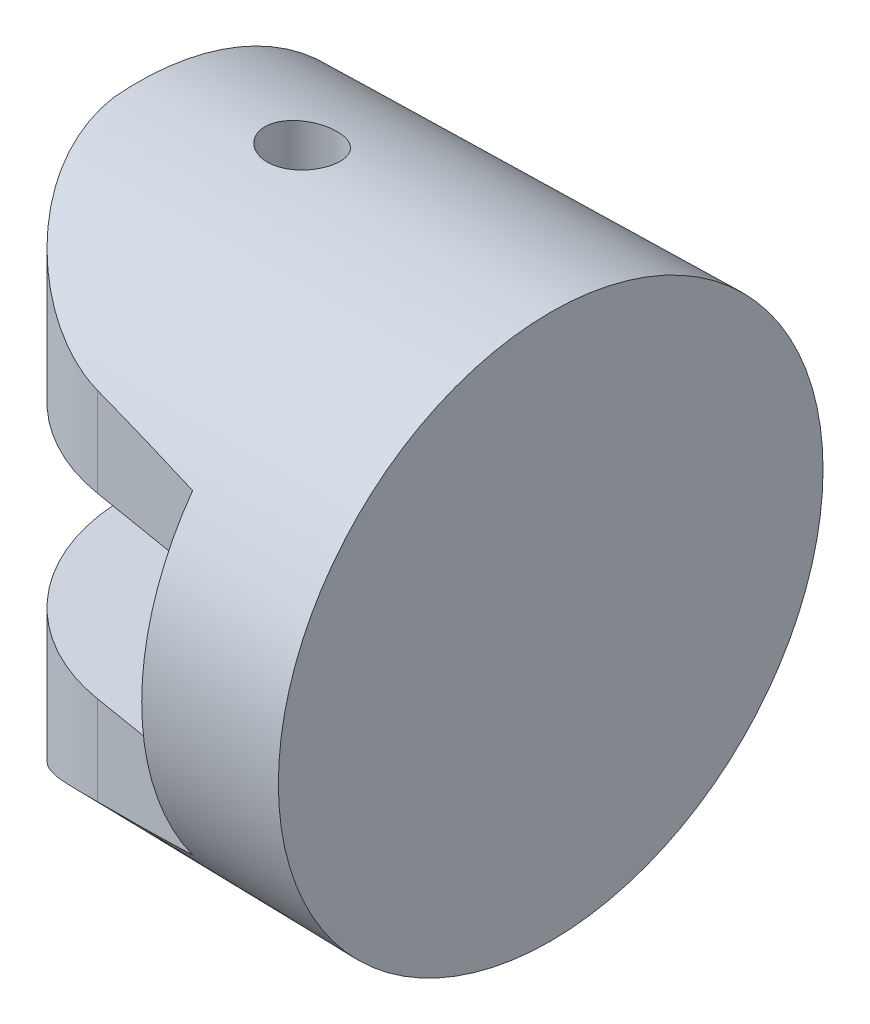
SolidWorks part; units mm, degrees
ref_plane "Ön Düzlem" through (0, 0, 0) normal (0, 0, 1) x (1, 0, 0)
ref_plane "Üst Düzlem" through (0, 0, 0) normal (0, 1, 0) x (1, 0, 0)
ref_plane "Sağ Düzlem" through (0, 0, 0) normal (1, 0, 0) x (0, 0, -1)
sketch "Sketch1" plane through (0, 0, 0) normal (1, 0, 0) x (0, 0, -1)
  circle A0 centre (0, 0) radius 10
  dimension "D1" = 20
extrude "Boss-Extrude1" add sketch "Sketch1" along normal blind 18
sketch "Sketch2" plane through (0, 0, 0) normal (0, 1, 0) x (1, 0, 0)
  line L0 (10, 9.0632) -> (0, 9.0632)
  line L1 (18, -10) -> (18, 10) construction
  line L2 (10, -8) -> (5.8413, -7.3121)
  line L3 (0, 9.0632) -> (0, -0.8843)
  line L5 (0, 10) -> (0, -10) construction
  line L6 (10, -8) -> (10, -11.2528)
  line L9 (10, -11.2528) -> (-2.5986, -11.2528)
  line L10 (-2.5986, -11.2528) -> (-2.5986, 12.4635)
  line L11 (-2.5986, 12.4635) -> (10, 12.4635)
  line L12 (10, 12.4635) -> (10, 9.0632)
  arc A0 (0, -0.8843) -> (5.8413, -7.3121) centre (6.9836, -0.4059) ccw
  dimension "D2" = 7
  dimension "D1" = 8
  dimension "D4" = 8
  dimension "D5" = 2
extrude "Cut-Extrude1" cut sketch "Sketch2" against normal blind 18 and the other way blind 18 contours L11 L12 L0 L3 A0 L2 L6 L9 L10
sketch "Sketch4" plane through (0, 0, 0) normal (0, 1, 0) x (1, 0, 0)
  line L0 (10, 9.0632) -> (-1.0009, 9.0632)
  line L1 (10, -8) -> (-1.0009, -8)
  line L2 (-1.0009, -8) -> (-1.0009, 9.0632)
  line L3 (10, 9.0632) -> (10, -8)
sketch "Sketch5" plane through (0, 0, 0) normal (0, 1, 0) x (1, 0, 0)
  line L0 (18, 10) -> (18, 1) construction
  line L1 (18, -10) -> (18, 10) construction
  line L2 (18, 1) -> (5, 1) construction
  circle A0 centre (5, 1) radius 1.25
  dimension "D3" = 2.5
  dimension "D2" = 13
  dimension "D1" = 9
extrude "Cut-Extrude4" cut sketch "Sketch5" against normal through all and the other way through all
sketch "Sketch6" plane through (18, 0, 0) normal (1, 0, 0) x (0, 0, -1)
  circle A0 centre (0, 0) radius 10 construction
  circle A1 centre (0, 0) radius 10
extrude "Cut-Extrude-Thin2" cut sketch "Sketch6" against normal blind 23.25 draft 1 thin draft outward yes thin type one direction wall 10
fillet "Fillet1" radius 0.5 1 edges at (0, 0, -9.0632)
chamfer "Chamfer2" distance 1 angle 45 1 edges at (10, 0, -9.8604) first distance on face at (10, 0, -9.4618)
extrude "Cut-Extrude5" cut sketch "Sketch4" against normal blind 3.25 and the other way blind 3.25
sketch "Sketch7" plane through (0, 0, 0) normal (0, 1, 0) x (1, 0, 0)
  line L0 (15.0797, 11.4257) -> (15.0797, -12.0127)
  line L1 (15.0797, -12.0127) -> (19.9016, -12.0127)
  line L2 (19.9016, -12.0127) -> (19.9016, 11.4257)
  line L3 (19.9016, 11.4257) -> (15.0797, 11.4257)
extrude "Cut-Extrude6" cut sketch "Sketch7" against normal blind 15.25 and the other way blind 17
